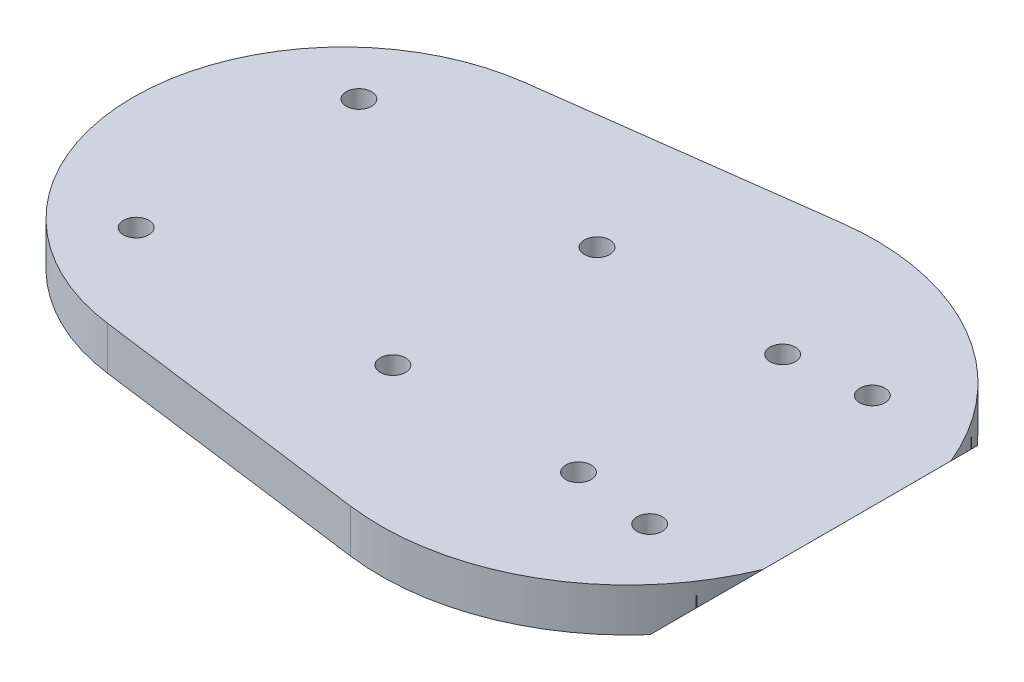
SolidWorks part; units mm, degrees
ref_plane "Front Plane" through (0, 0, 0) normal (0, 0, 1) x (1, 0, 0)
ref_plane "Top Plane" through (0, 0, 0) normal (0, 1, 0) x (1, 0, 0)
ref_plane "Right Plane" through (0, 0, 0) normal (1, 0, 0) x (0, 0, -1)
ref_plane "Plane1" through (0, 28, 0) normal (0, 1, 0) x (1, 0, 0)
sketch "Sketch1" plane through (0, 28, 0) normal (0, 1, 0) x (1, 0, 0)
  line L0 (256.0749, -319.2905) -> (301.2923, -313.3417)
  line L1 (301.2923, -392.6583) -> (256.0749, -386.7095)
  arc A0 (301.2923, -313.3417) -> (301.2923, -392.6583) centre (306.5097, -353) cw
  arc A1 (256.0749, -386.7095) -> (256.0749, -319.2905) centre (260.5097, -353) cw
extrude "Boss-Extrude1" add sketch "Sketch1" along normal blind 2
ref_plane "Plane2" through (0, 23, 0) normal (0, 1, 0) x (1, 0, 0)
sketch "Sketch2" plane through (0, 23, 0) normal (0, 1, 0) x (1, 0, 0)
  line L0 (256.0749, -319.2905) -> (301.2923, -313.3417)
  line L1 (301.2923, -392.6583) -> (256.0749, -386.7095)
  line L2 (256.2836, -320.8768) -> (301.501, -314.9281)
  line L3 (301.501, -391.0719) -> (256.2836, -385.1232)
  arc A0 (301.2923, -313.3417) -> (301.2923, -392.6583) centre (306.5097, -353) cw
  arc A1 (256.0749, -386.7095) -> (256.0749, -319.2905) centre (260.5097, -353) cw
  arc A2 (301.501, -314.9281) -> (301.501, -391.0719) centre (306.5097, -353) cw
  arc A3 (256.2836, -385.1232) -> (256.2836, -320.8768) centre (260.5097, -353) cw
extrude "Boss-Extrude2" add sketch "Sketch2" along normal blind 5
sketch "Sketch3" plane through (0, 23, 0) normal (0, 1, 0) x (1, 0, 0)
  line L0 (237.2, -328.6184) -> (238.8, -328.6184)
  line L1 (238.8, -328.6184) -> (238.8, -377.3816)
  line L2 (238.8, -377.3816) -> (237.2, -377.3816)
  line L3 (237.2, -377.3816) -> (237.2, -328.6184)
extrude "Boss-Extrude3" add sketch "Sketch3" along normal blind 5
sketch "Sketch4" plane through (0, 23, 0) normal (0, 1, 0) x (1, 0, 0)
  line L0 (252.2, -320.9397) -> (253.8, -320.9397)
  line L1 (253.8, -320.9397) -> (253.8, -385.0603)
  line L2 (253.8, -385.0603) -> (252.2, -385.0603)
  line L3 (252.2, -385.0603) -> (252.2, -320.9397)
extrude "Boss-Extrude4" add sketch "Sketch4" along normal blind 5
sketch "Sketch5" plane through (0, 23, 0) normal (0, 1, 0) x (1, 0, 0)
  line L0 (267.2, -320.0019) -> (268.8, -320.0019)
  line L1 (268.8, -320.0019) -> (268.8, -385.9981)
  line L2 (268.8, -385.9981) -> (267.2, -385.9981)
  line L3 (267.2, -385.9981) -> (267.2, -320.0019)
extrude "Boss-Extrude5" add sketch "Sketch5" along normal blind 5
sketch "Sketch6" plane through (0, 23, 0) normal (0, 1, 0) x (1, 0, 0)
  line L0 (326.2, -319.7467) -> (327.8, -319.7467)
  line L1 (327.8, -319.7467) -> (327.8, -386.2533)
  line L2 (327.8, -386.2533) -> (326.2, -386.2533)
  line L3 (326.2, -386.2533) -> (326.2, -319.7467)
extrude "Boss-Extrude6" add sketch "Sketch6" along normal blind 5
sketch "Sketch7" plane through (0, 23, 0) normal (0, 1, 0) x (1, 0, 0)
  line L0 (338.2, -330.768) -> (339.8, -330.768)
  line L1 (339.8, -330.768) -> (339.8, -375.232)
  line L2 (339.8, -375.232) -> (338.2, -375.232)
  line L3 (338.2, -375.232) -> (338.2, -330.768)
extrude "Boss-Extrude7" add sketch "Sketch7" along normal blind 5
sketch "Sketch8" plane through (0, 23, 0) normal (0, 1, 0) x (1, 0, 0)
  line L0 (295, -336) -> (305, -336)
  line L1 (305, -370) -> (295, -370)
  line L2 (295, -337.6) -> (305, -337.6)
  line L3 (305, -368.4) -> (295, -368.4)
  arc A0 (305, -336) -> (305, -370) centre (305, -353) cw
  arc A1 (295, -370) -> (295, -336) centre (295, -353) cw
  arc A2 (305, -337.6) -> (305, -368.4) centre (305, -353) cw
  arc A3 (295, -368.4) -> (295, -337.6) centre (295, -353) cw
extrude "Boss-Extrude8" add sketch "Sketch8" along normal blind 5
sketch "Sketch9" plane through (0, 23, 0) normal (0, 1, 0) x (1, 0, 0)
  circle A0 centre (285, -336.5) radius 5.05
extrude "Boss-Extrude9" add sketch "Sketch9" along normal blind 5
sketch "Sketch10" plane through (0, 23, 0) normal (0, 1, 0) x (1, 0, 0)
  circle A0 centre (285, -369.5) radius 5.05
extrude "Boss-Extrude10" add sketch "Sketch10" along normal blind 5
sketch "Sketch11" plane through (0, 23, 0) normal (0, 1, 0) x (1, 0, 0)
  circle A0 centre (315, -336.5) radius 5.05
extrude "Boss-Extrude11" add sketch "Sketch11" along normal blind 5
sketch "Sketch12" plane through (0, 23, 0) normal (0, 1, 0) x (1, 0, 0)
  circle A0 centre (315, -369.5) radius 5.05
extrude "Boss-Extrude12" add sketch "Sketch12" along normal blind 5
sketch "Sketch13" plane through (0, 23, 0) normal (0, 1, 0) x (1, 0, 0)
  circle A0 centre (328, -335) radius 5.05
extrude "Boss-Extrude13" add sketch "Sketch13" along normal blind 5
sketch "Sketch14" plane through (0, 23, 0) normal (0, 1, 0) x (1, 0, 0)
  circle A0 centre (328, -371) radius 5.05
extrude "Boss-Extrude14" add sketch "Sketch14" along normal blind 5
sketch "Sketch15" plane through (0, 23, 0) normal (0, 1, 0) x (1, 0, 0)
  circle A0 centre (245, -335) radius 5.05
extrude "Boss-Extrude15" add sketch "Sketch15" along normal blind 5
sketch "Sketch16" plane through (0, 23, 0) normal (0, 1, 0) x (1, 0, 0)
  circle A0 centre (245, -371) radius 5.05
extrude "Boss-Extrude16" add sketch "Sketch16" along normal blind 5
ref_plane "Plane3" through (0, 26.8, 0) normal (0, 1, 0) x (1, 0, 0)
sketch "Sketch17" plane through (0, 26.8, 0) normal (0, 1, 0) x (1, 0, 0)
  circle A0 centre (232.5097, -337.8127) radius 0.5
  circle A1 centre (232.5097, -340.3127) radius 0.5
  circle A2 centre (232.5097, -342.8127) radius 0.5
  circle A3 centre (232.5097, -345.3127) radius 0.5
  circle A4 centre (232.5097, -347.8127) radius 0.5
  circle A5 centre (232.5097, -350.3127) radius 0.5
  circle A6 centre (232.5097, -352.8127) radius 0.5
  circle A7 centre (232.5097, -355.3127) radius 0.5
  circle A8 centre (232.5097, -357.8127) radius 0.5
  circle A9 centre (232.5097, -360.3127) radius 0.5
  circle A10 centre (232.5097, -362.8127) radius 0.5
  circle A11 centre (232.5097, -365.3127) radius 0.5
  circle A12 centre (232.5097, -367.8127) radius 0.5
  circle A13 centre (235.0097, -334.6111) radius 0.5
  circle A14 centre (235.0097, -337.1111) radius 0.5
  circle A15 centre (235.0097, -339.6111) radius 0.5
  circle A16 centre (235.0097, -342.1111) radius 0.5
  circle A17 centre (235.0097, -344.6111) radius 0.5
  circle A18 centre (235.0097, -347.1111) radius 0.5
  circle A19 centre (235.0097, -349.6111) radius 0.5
  circle A20 centre (235.0097, -352.1111) radius 0.5
  circle A21 centre (235.0097, -354.6111) radius 0.5
  circle A22 centre (235.0097, -357.1111) radius 0.5
  circle A23 centre (235.0097, -359.6111) radius 0.5
  circle A24 centre (235.0097, -362.1111) radius 0.5
  circle A25 centre (235.0097, -364.6111) radius 0.5
  circle A26 centre (235.0097, -367.1111) radius 0.5
  circle A27 centre (235.0097, -369.6111) radius 0.5
  circle A28 centre (242.5097, -328.2556) radius 0.5
  circle A29 centre (242.5097, -343.2556) radius 0.5
  circle A30 centre (242.5097, -345.7556) radius 0.5
  circle A31 centre (242.5097, -348.2556) radius 0.5
  circle A32 centre (242.5097, -350.7556) radius 0.5
  circle A33 centre (242.5097, -353.2556) radius 0.5
  circle A34 centre (242.5097, -355.7556) radius 0.5
  circle A35 centre (242.5097, -358.2556) radius 0.5
  circle A36 centre (242.5097, -360.7556) radius 0.5
  circle A37 centre (242.5097, -363.2556) radius 0.5
  circle A38 centre (245.0097, -326.8386) radius 0.5
  circle A39 centre (245.0097, -341.8386) radius 0.5
  circle A40 centre (245.0097, -344.3386) radius 0.5
  circle A41 centre (245.0097, -346.8386) radius 0.5
  circle A42 centre (245.0097, -349.3386) radius 0.5
  circle A43 centre (245.0097, -351.8386) radius 0.5
  circle A44 centre (245.0097, -354.3386) radius 0.5
  circle A45 centre (245.0097, -356.8386) radius 0.5
  circle A46 centre (245.0097, -359.3386) radius 0.5
  circle A47 centre (245.0097, -361.8386) radius 0.5
  circle A48 centre (245.0097, -364.3386) radius 0.5
  circle A49 centre (247.5097, -325.6834) radius 0.5
  circle A50 centre (247.5097, -328.1834) radius 0.5
  circle A51 centre (247.5097, -343.1834) radius 0.5
  circle A52 centre (247.5097, -345.6834) radius 0.5
  circle A53 centre (247.5097, -348.1834) radius 0.5
  circle A54 centre (247.5097, -350.6834) radius 0.5
  circle A55 centre (247.5097, -353.1834) radius 0.5
  circle A56 centre (247.5097, -355.6834) radius 0.5
  circle A57 centre (247.5097, -358.1834) radius 0.5
  circle A58 centre (247.5097, -360.6834) radius 0.5
  circle A59 centre (247.5097, -363.1834) radius 0.5
  circle A60 centre (247.5097, -378.1834) radius 0.5
  circle A61 centre (250.0097, -324.7619) radius 0.5
  circle A62 centre (250.0097, -327.2619) radius 0.5
  circle A63 centre (250.0097, -329.7619) radius 0.5
  circle A64 centre (250.0097, -339.7619) radius 0.5
  circle A65 centre (250.0097, -342.2619) radius 0.5
  circle A66 centre (250.0097, -344.7619) radius 0.5
  circle A67 centre (250.0097, -347.2619) radius 0.5
  circle A68 centre (250.0097, -349.7619) radius 0.5
  circle A69 centre (250.0097, -352.2619) radius 0.5
  circle A70 centre (250.0097, -354.7619) radius 0.5
  circle A71 centre (250.0097, -357.2619) radius 0.5
  circle A72 centre (250.0097, -359.7619) radius 0.5
  circle A73 centre (250.0097, -362.2619) radius 0.5
  circle A74 centre (250.0097, -364.7619) radius 0.5
  circle A75 centre (250.0097, -377.2619) radius 0.5
  circle A76 centre (250.0097, -379.7619) radius 0.5
  circle A77 centre (257.5097, -323.2326) radius 0.5
  circle A78 centre (257.5097, -325.7326) radius 0.5
  circle A79 centre (257.5097, -328.2326) radius 0.5
  circle A80 centre (257.5097, -330.7326) radius 0.5
  circle A81 centre (257.5097, -333.2326) radius 0.5
  circle A82 centre (257.5097, -335.7326) radius 0.5
  circle A83 centre (257.5097, -338.2326) radius 0.5
  circle A84 centre (257.5097, -340.7326) radius 0.5
  circle A85 centre (257.5097, -343.2326) radius 0.5
  circle A86 centre (257.5097, -345.7326) radius 0.5
  circle A87 centre (257.5097, -348.2326) radius 0.5
  circle A88 centre (257.5097, -350.7326) radius 0.5
  circle A89 centre (257.5097, -353.2326) radius 0.5
  circle A90 centre (257.5097, -355.7326) radius 0.5
  circle A91 centre (257.5097, -358.2326) radius 0.5
  circle A92 centre (257.5097, -360.7326) radius 0.5
  circle A93 centre (257.5097, -363.2326) radius 0.5
  circle A94 centre (257.5097, -365.7326) radius 0.5
  circle A95 centre (257.5097, -368.2326) radius 0.5
  circle A96 centre (257.5097, -370.7326) radius 0.5
  circle A97 centre (257.5097, -373.2326) radius 0.5
  circle A98 centre (257.5097, -375.7326) radius 0.5
  circle A99 centre (257.5097, -378.2326) radius 0.5
  circle A100 centre (257.5097, -380.7326) radius 0.5
  circle A101 centre (260.0097, -323.1037) radius 0.5
  circle A102 centre (260.0097, -325.6037) radius 0.5
  circle A103 centre (260.0097, -328.1037) radius 0.5
  circle A104 centre (260.0097, -330.6037) radius 0.5
  circle A105 centre (260.0097, -333.1037) radius 0.5
  circle A106 centre (260.0097, -335.6037) radius 0.5
  circle A107 centre (260.0097, -338.1037) radius 0.5
  circle A108 centre (260.0097, -340.6037) radius 0.5
  circle A109 centre (260.0097, -343.1037) radius 0.5
  circle A110 centre (260.0097, -345.6037) radius 0.5
  circle A111 centre (260.0097, -348.1037) radius 0.5
  circle A112 centre (260.0097, -350.6037) radius 0.5
  circle A113 centre (260.0097, -353.1037) radius 0.5
  circle A114 centre (260.0097, -355.6037) radius 0.5
  circle A115 centre (260.0097, -358.1037) radius 0.5
  circle A116 centre (260.0097, -360.6037) radius 0.5
  circle A117 centre (260.0097, -363.1037) radius 0.5
  circle A118 centre (260.0097, -365.6037) radius 0.5
  circle A119 centre (260.0097, -368.1037) radius 0.5
  circle A120 centre (260.0097, -370.6037) radius 0.5
  circle A121 centre (260.0097, -373.1037) radius 0.5
  circle A122 centre (260.0097, -375.6037) radius 0.5
  circle A123 centre (260.0097, -378.1037) radius 0.5
  circle A124 centre (260.0097, -380.6037) radius 0.5
  circle A125 centre (262.5097, -323.1589) radius 0.5
  circle A126 centre (262.5097, -325.6589) radius 0.5
  circle A127 centre (262.5097, -328.1589) radius 0.5
  circle A128 centre (262.5097, -330.6589) radius 0.5
  circle A129 centre (262.5097, -333.1589) radius 0.5
  circle A130 centre (262.5097, -335.6589) radius 0.5
  circle A131 centre (262.5097, -338.1589) radius 0.5
  circle A132 centre (262.5097, -340.6589) radius 0.5
  circle A133 centre (262.5097, -343.1589) radius 0.5
  circle A134 centre (262.5097, -345.6589) radius 0.5
  circle A135 centre (262.5097, -348.1589) radius 0.5
  circle A136 centre (262.5097, -350.6589) radius 0.5
  circle A137 centre (262.5097, -353.1589) radius 0.5
  circle A138 centre (262.5097, -355.6589) radius 0.5
  circle A139 centre (262.5097, -358.1589) radius 0.5
  circle A140 centre (262.5097, -360.6589) radius 0.5
  circle A141 centre (262.5097, -363.1589) radius 0.5
  circle A142 centre (262.5097, -365.6589) radius 0.5
  circle A143 centre (262.5097, -368.1589) radius 0.5
  circle A144 centre (262.5097, -370.6589) radius 0.5
  circle A145 centre (262.5097, -373.1589) radius 0.5
  circle A146 centre (262.5097, -375.6589) radius 0.5
  circle A147 centre (262.5097, -378.1589) radius 0.5
  circle A148 centre (262.5097, -380.6589) radius 0.5
  circle A149 centre (265.0097, -323.3822) radius 0.5
  circle A150 centre (265.0097, -325.8822) radius 0.5
  circle A151 centre (265.0097, -328.3822) radius 0.5
  circle A152 centre (265.0097, -330.8822) radius 0.5
  circle A153 centre (265.0097, -333.3822) radius 0.5
  circle A154 centre (265.0097, -335.8822) radius 0.5
  circle A155 centre (265.0097, -338.3822) radius 0.5
  circle A156 centre (265.0097, -340.8822) radius 0.5
  circle A157 centre (265.0097, -343.3822) radius 0.5
  circle A158 centre (265.0097, -345.8822) radius 0.5
  circle A159 centre (265.0097, -348.3822) radius 0.5
  circle A160 centre (265.0097, -350.8822) radius 0.5
  circle A161 centre (265.0097, -353.3822) radius 0.5
  circle A162 centre (265.0097, -355.8822) radius 0.5
  circle A163 centre (265.0097, -358.3822) radius 0.5
  circle A164 centre (265.0097, -360.8822) radius 0.5
  circle A165 centre (265.0097, -363.3822) radius 0.5
  circle A166 centre (265.0097, -365.8822) radius 0.5
  circle A167 centre (265.0097, -368.3822) radius 0.5
  circle A168 centre (265.0097, -370.8822) radius 0.5
  circle A169 centre (265.0097, -373.3822) radius 0.5
  circle A170 centre (265.0097, -375.8822) radius 0.5
  circle A171 centre (265.0097, -378.3822) radius 0.5
  circle A172 centre (265.0097, -380.8822) radius 0.5
  circle A173 centre (272.5097, -322.4285) radius 0.5
  circle A174 centre (272.5097, -324.9285) radius 0.5
  circle A175 centre (272.5097, -327.4285) radius 0.5
  circle A176 centre (272.5097, -329.9285) radius 0.5
  circle A177 centre (272.5097, -332.4285) radius 0.5
  circle A178 centre (272.5097, -334.9285) radius 0.5
  circle A179 centre (272.5097, -337.4285) radius 0.5
  circle A180 centre (272.5097, -339.9285) radius 0.5
  circle A181 centre (272.5097, -342.4285) radius 0.5
  circle A182 centre (272.5097, -344.9285) radius 0.5
  circle A183 centre (272.5097, -347.4285) radius 0.5
  circle A184 centre (272.5097, -349.9285) radius 0.5
  circle A185 centre (272.5097, -352.4285) radius 0.5
  circle A186 centre (272.5097, -354.9285) radius 0.5
  circle A187 centre (272.5097, -357.4285) radius 0.5
  circle A188 centre (272.5097, -359.9285) radius 0.5
  circle A189 centre (272.5097, -362.4285) radius 0.5
  circle A190 centre (272.5097, -364.9285) radius 0.5
  circle A191 centre (272.5097, -367.4285) radius 0.5
  circle A192 centre (272.5097, -369.9285) radius 0.5
  circle A193 centre (272.5097, -372.4285) radius 0.5
  circle A194 centre (272.5097, -374.9285) radius 0.5
  circle A195 centre (272.5097, -377.4285) radius 0.5
  circle A196 centre (272.5097, -379.9285) radius 0.5
  circle A197 centre (272.5097, -382.4285) radius 0.5
  circle A198 centre (275.0097, -322.1106) radius 0.5
  circle A199 centre (275.0097, -324.6106) radius 0.5
  circle A200 centre (275.0097, -327.1106) radius 0.5
  circle A201 centre (275.0097, -329.6106) radius 0.5
  circle A202 centre (275.0097, -332.1106) radius 0.5
  circle A203 centre (275.0097, -334.6106) radius 0.5
  circle A204 centre (275.0097, -337.1106) radius 0.5
  circle A205 centre (275.0097, -339.6106) radius 0.5
  circle A206 centre (275.0097, -342.1106) radius 0.5
  circle A207 centre (275.0097, -344.6106) radius 0.5
  circle A208 centre (275.0097, -347.1106) radius 0.5
  circle A209 centre (275.0097, -349.6106) radius 0.5
  circle A210 centre (275.0097, -352.1106) radius 0.5
  circle A211 centre (275.0097, -354.6106) radius 0.5
  circle A212 centre (275.0097, -357.1106) radius 0.5
  circle A213 centre (275.0097, -359.6106) radius 0.5
  circle A214 centre (275.0097, -362.1106) radius 0.5
  circle A215 centre (275.0097, -364.6106) radius 0.5
  circle A216 centre (275.0097, -367.1106) radius 0.5
  circle A217 centre (275.0097, -369.6106) radius 0.5
  circle A218 centre (275.0097, -372.1106) radius 0.5
  circle A219 centre (275.0097, -374.6106) radius 0.5
  circle A220 centre (275.0097, -377.1106) radius 0.5
  circle A221 centre (275.0097, -379.6106) radius 0.5
  circle A222 centre (275.0097, -382.1106) radius 0.5
  circle A223 centre (330.0097, -324.731) radius 0.5
  circle A224 centre (330.0097, -327.231) radius 0.5
  circle A225 centre (330.0097, -342.231) radius 0.5
  circle A226 centre (330.0097, -344.731) radius 0.5
  circle A227 centre (330.0097, -347.231) radius 0.5
  circle A228 centre (330.0097, -349.731) radius 0.5
  circle A229 centre (330.0097, -352.231) radius 0.5
  circle A230 centre (330.0097, -354.731) radius 0.5
  circle A231 centre (330.0097, -357.231) radius 0.5
  circle A232 centre (330.0097, -359.731) radius 0.5
  circle A233 centre (330.0097, -362.231) radius 0.5
  circle A234 centre (330.0097, -364.731) radius 0.5
  circle A235 centre (330.0097, -379.731) radius 0.5
  circle A236 centre (332.5097, -326.7026) radius 0.5
  circle A237 centre (332.5097, -329.2026) radius 0.5
  circle A238 centre (332.5097, -341.7026) radius 0.5
  circle A239 centre (332.5097, -344.2026) radius 0.5
  circle A240 centre (332.5097, -346.7026) radius 0.5
  circle A241 centre (332.5097, -349.2026) radius 0.5
  circle A242 centre (332.5097, -351.7026) radius 0.5
  circle A243 centre (332.5097, -354.2026) radius 0.5
  circle A244 centre (332.5097, -356.7026) radius 0.5
  circle A245 centre (332.5097, -359.2026) radius 0.5
  circle A246 centre (332.5097, -361.7026) radius 0.5
  circle A247 centre (332.5097, -364.2026) radius 0.5
  circle A248 centre (332.5097, -376.7026) radius 0.5
  circle A249 centre (332.5097, -379.2026) radius 0.5
  circle A250 centre (335.0097, -329.0331) radius 0.5
  circle A251 centre (335.0097, -331.5331) radius 0.5
  circle A252 centre (335.0097, -334.0331) radius 0.5
  circle A253 centre (335.0097, -336.5331) radius 0.5
  circle A254 centre (335.0097, -339.0331) radius 0.5
  circle A255 centre (335.0097, -341.5331) radius 0.5
  circle A256 centre (335.0097, -344.0331) radius 0.5
  circle A257 centre (335.0097, -346.5331) radius 0.5
  circle A258 centre (335.0097, -349.0331) radius 0.5
  circle A259 centre (335.0097, -351.5331) radius 0.5
  circle A260 centre (335.0097, -354.0331) radius 0.5
  circle A261 centre (335.0097, -356.5331) radius 0.5
  circle A262 centre (335.0097, -359.0331) radius 0.5
  circle A263 centre (335.0097, -361.5331) radius 0.5
  circle A264 centre (335.0097, -364.0331) radius 0.5
  circle A265 centre (335.0097, -366.5331) radius 0.5
  circle A266 centre (335.0097, -369.0331) radius 0.5
  circle A267 centre (335.0097, -371.5331) radius 0.5
  circle A268 centre (335.0097, -374.0331) radius 0.5
  circle A269 centre (335.0097, -376.5331) radius 0.5
extrude "Boss-Extrude17" add sketch "Sketch17" along normal blind 1.2
ref_plane "Plane4" through (0, 23.3, 0) normal (0, 1, 0) x (1, 0, 0)
sketch "Sketch18" plane through (0, 23.3, 0) normal (0, 1, 0) x (1, 0, 0)
  circle A0 centre (285, -336.5) radius 2.05
  circle A1 centre (285, -369.5) radius 2.05
  circle A2 centre (315, -336.5) radius 2.05
  circle A3 centre (315, -369.5) radius 2.05
extrude "Cut-Extrude1" cut sketch "Sketch18" along normal blind 6.7
sketch "Sketch19" plane through (0, 23.3, 0) normal (0, 1, 0) x (1, 0, 0)
  circle A0 centre (328, -335) radius 2.05
  circle A1 centre (328, -371) radius 2.05
  circle A2 centre (245, -335) radius 2.05
  circle A3 centre (245, -371) radius 2.05
extrude "Cut-Extrude2" cut sketch "Sketch19" along normal blind 6.7
ref_plane "Plane5" through (0, 22, 0) normal (0, 1, 0) x (1, 0, 0)
sketch "Sketch20" plane through (0, 22, 0) normal (0, 1, 0) x (1, 0, 0)
  circle A0 centre (328, -335) radius 1.6
  circle A1 centre (328, -371) radius 1.6
  circle A2 centre (245, -335) radius 1.6
  circle A3 centre (245, -371) radius 1.6
extrude "Cut-Extrude3" cut sketch "Sketch20" along normal blind 8
ref_plane "Plane6" through (0, 0, 273) normal (0, 0, 1) x (1, 0, 0)
sketch "Sketch21" plane through (0, 0, 273) normal (0, 0, 1) x (1, 0, 0)
  line L0 (336.5097, 22.99) -> (348.5097, 22.99)
  line L1 (348.5097, 22.99) -> (348.5097, 35)
  line L2 (348.5097, 35) -> (336.5097, 22.99)
extrude "Cut-Extrude4" cut sketch "Sketch21" along normal blind 160
